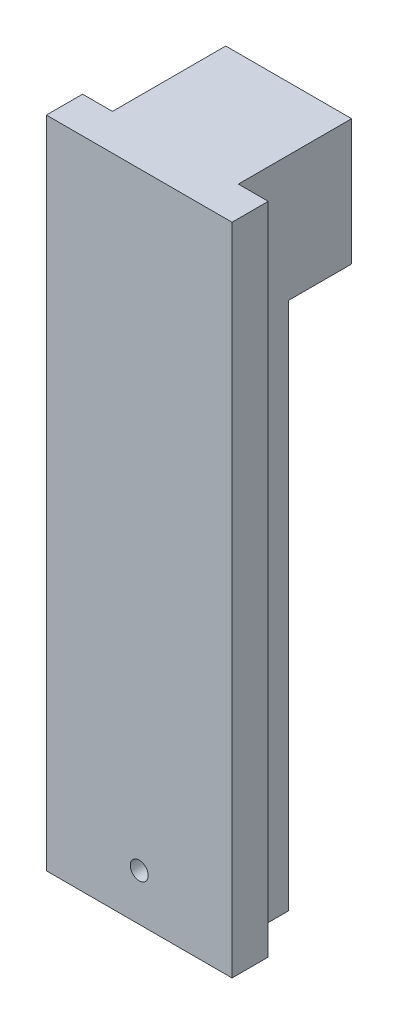
SolidWorks part; units mm, degrees
ref_plane "Płaszczyzna przednia" through (0, 0, 0) normal (0, 0, 1) x (1, 0, 0)
ref_plane "Płaszczyzna górna" through (0, 0, 0) normal (0, 1, 0) x (1, 0, 0)
ref_plane "Płaszczyzna prawa" through (0, 0, 0) normal (1, 0, 0) x (0, 0, -1)
sketch "Szkic1" plane through (0, 0, 0) normal (0, 1, 0) x (1, 0, 0)
  line L0 (0, -6) -> (0, 0) construction
  line L1 (0, 13.75) -> (0, 0) construction
  line L7 (-14.75, 0) -> (14.75, 0)
  line L8 (19.5, 5.75) -> (10, 5.75) construction
  line L10 (14.75, 0) -> (14.75, 5.75)
  line L11 (14.75, 5.75) -> (10, 5.75)
  line L12 (10, 5.75) -> (10, 13.75)
  line L13 (10, 13.75) -> (-10, 13.75)
  line L14 (-10, 13.75) -> (-10, 5.75)
  line L15 (-10, 5.75) -> (-14.75, 5.75)
  line L16 (-14.75, 5.75) -> (-14.75, 0)
  dimension "D1" = 6
  dimension "D4" = 9.5
  dimension "D5" = 29.5
  dimension "D6" = 20
  dimension "D7" = 5.75
  dimension "D8" = 4.75
  dimension "D9" = 29.5
  dimension "D10" = 20
  dimension "D11" = 20
  dimension "D12" = 8
extrude "Dodanie-wyciągnięcie1" add sketch "Szkic1" along normal blind 104
sketch "Szkic2" plane through (0, 0, -13.75) normal (0, 0, -1) x (-1, 0, 0)
  line L0 (-10, 104) -> (10, 104)
  line L1 (10, 104) -> (10, 84)
  line L2 (10, 104) -> (10, 0) construction
  line L3 (10, 84) -> (-10, 84)
  line L4 (-10, 104) -> (-10, 0) construction
  line L5 (-10, 84) -> (-10, 104)
  dimension "D1" = 20
extrude "Dodanie-wyciągnięcie2" add sketch "Szkic2" along normal blind 10
sketch "Szkic3" plane through (0, 0, -23.75) normal (0, 0, -1) x (-1, 0, 0)
  line L0 (-10, 94) -> (10, 94) construction
  line L1 (-10, 104) -> (-10, 84) construction
  line L2 (10, 84) -> (10, 104) construction
  line L3 (0, 104) -> (0, 84) construction
  line L4 (10, 104) -> (-10, 104) construction
  line L5 (-10, 84) -> (10, 84) construction
  circle A0 centre (0, 94) radius 2.5
  dimension "D1" = 5
extrude "Wytnij-wyciągnięcie1" cut sketch "Szkic3" against normal blind 10
sketch "Szkic4" plane through (0, 0, 0) normal (0, 0, 1) x (1, 0, 0)
  line L0 (0, 0) -> (0, 6) construction
  circle A0 centre (0, 7.425) radius 1.425
  dimension "D2" = 2.85
  dimension "D1" = 6
extrude "Wytnij-wyciągnięcie2" cut sketch "Szkic4" against normal through all
